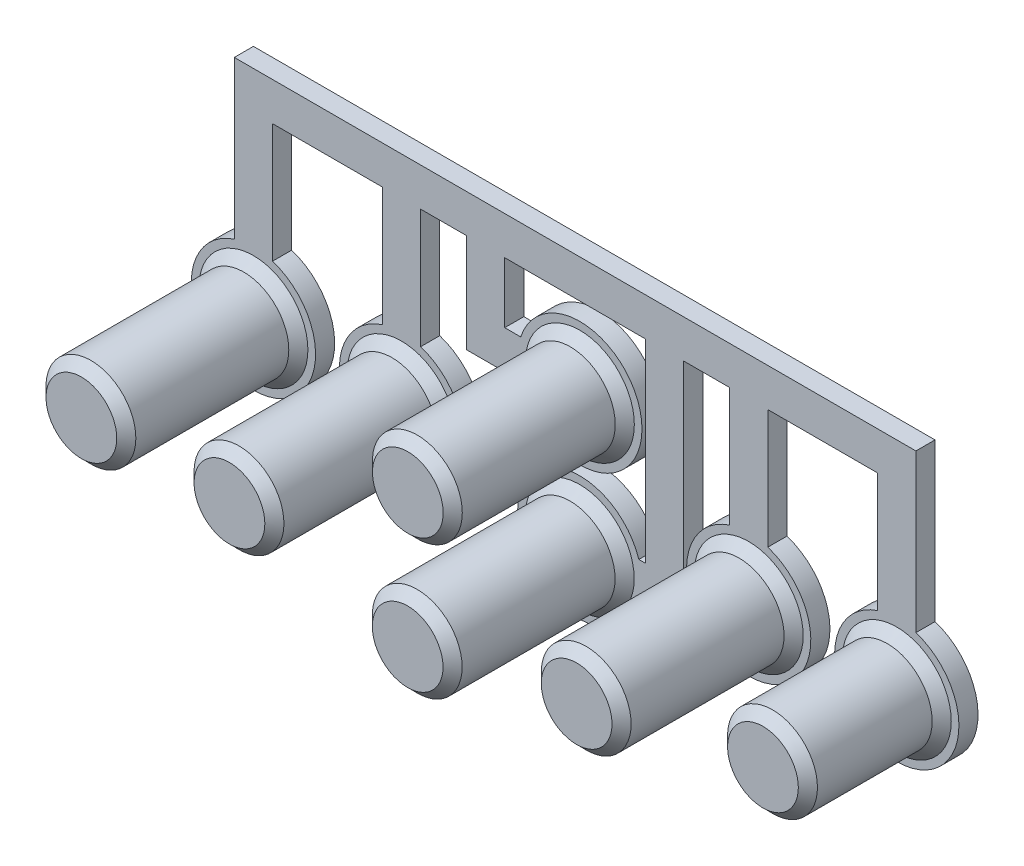
SolidWorks part; units mm, degrees
ref_plane "Front Plane" through (0, 0, 0) normal (0, 0, 1) x (1, 0, 0)
ref_plane "Top Plane" through (0, 0, 0) normal (0, 1, 0) x (1, 0, 0)
ref_plane "Right Plane" through (0, 0, 0) normal (1, 0, 0) x (0, 0, -1)
sketch "Skizze1" plane through (0, 0, 0) normal (0, 0, 1) x (1, 0, 0)
  line L0 (0.0076, 9.9935) -> (0.0076, 3.9935) construction
  line L1 (-2.9924, 9.9935) -> (3.0076, 9.9935) construction
  line L2 (3.0076, 3.9935) -> (-2.9924, 3.9935) construction
  line L3 (8.8392, 4.8386) -> (8.8392, -1.1614) construction
  line L4 (5.8392, 4.8386) -> (11.8392, 4.8386) construction
  line L5 (11.8392, -1.1614) -> (5.8392, -1.1614) construction
  line L6 (16.5862, 4.8386) -> (16.5862, -1.1614) construction
  line L7 (13.5862, 4.8386) -> (19.5862, 4.8386) construction
  line L8 (19.5862, -1.1614) -> (13.5862, -1.1614) construction
  line L9 (-9.3218, 4.8386) -> (-9.3218, -1.1614) construction
  line L10 (-12.3218, 4.8386) -> (-6.3218, 4.8386) construction
  line L11 (-6.3218, -1.1614) -> (-12.3218, -1.1614) construction
  line L12 (-17.0688, 4.8386) -> (-17.0688, -1.1614) construction
  line L13 (-20.0688, 4.8386) -> (-14.0688, 4.8386) construction
  line L14 (-14.0688, -1.1614) -> (-20.0688, -1.1614) construction
  circle A0 centre (0, 0) radius 2.35
  circle A1 centre (0.0076, 6.9935) radius 2.35
  circle A2 centre (8.8392, 1.8386) radius 2.35
  circle A3 centre (16.5862, 1.8386) radius 2.35
  circle A4 centre (-9.3218, 1.8386) radius 2.35
  circle A5 centre (-17.0688, 1.8386) radius 2.35
  dimension "D2" = 4.7
extrude "Aufsatz-Linear austragen1" add sketch "Skizze1" along normal blind 10 contours A5 | A4 | A0 | A1 | A2 region at (0, 0, 0) region at (0.0076, 6.9935, 0) region at (8.8392, 1.8386, 0) region at (-9.3218, 1.8386, 0) region at (-17.0688, 1.8386, 0)
extrude "Aufsatz-Linear austragen4" add sketch "Skizze1<3>" along normal blind 8 contours A3 region at (16.5862, 1.8386, 0)
sketch "Skizze1<3>" plane through (0, 0, 0) normal (0, 0, 1) x (1, 0, 0) same geometry as "Skizze1"
sketch "Skizze2" plane through (0, 0, 0) normal (0, 0, 1) x (1, 0, 0)
  circle A0 centre (-17.0688, 1.8386) radius 3.25
  circle A1 centre (-9.3218, 1.8386) radius 3.25
  circle A2 centre (0, 0) radius 3.25
  circle A3 centre (0.0076, 6.9935) radius 3.25
  circle A4 centre (8.8392, 1.8386) radius 3.25
  circle A5 centre (16.5862, 1.8386) radius 3.25
  dimension "D1" = 6.5
extrude "Aufsatz-Linear austragen2" add sketch "Skizze2" along normal blind 1
sketch "Skizze3" plane through (0, 0, 0) normal (0, 0, 1) x (1, 0, 0)
  line L0 (-17.0688, 1.8386) -> (-17.0688, 14.2266) construction
  line L1 (-18.0688, 13.1646) -> (-18.0688, 4.9309)
  line L2 (16.5862, 1.8386) -> (16.5862, 15.6024) construction
  line L3 (-18.0688, 13.1646) -> (17.5862, 13.1646)
  line L4 (17.5862, 13.1646) -> (17.5862, 4.9309)
  line L5 (-16.0688, 11.1646) -> (-16.0688, 4.9309)
  line L6 (-17.0688, 12.1646) -> (16.5862, 12.1646) construction
  line L7 (-16.0688, 11.1646) -> (-10.3218, 11.1646)
  line L8 (15.5862, 11.1646) -> (15.5862, 4.9309)
  line L9 (-16.0688, 11.1646) -> (-16.0688, 13.1646) construction
  line L10 (-9.3218, 1.8386) -> (-9.3218, 15.4604) construction
  line L11 (-8.3218, 11.1646) -> (-8.3218, 4.9309)
  line L12 (-10.3218, 11.1646) -> (-10.3218, 4.9309)
  line L13 (-8.3218, 11.1646) -> (-5.9218, 11.1646)
  line L14 (-4.9218, 11.1646) -> (-4.9218, 0.7573) construction
  line L15 (0.0076, 6.9935) -> (-4.9218, 6.9935) construction
  line L16 (-3.9218, 7.9935) -> (-3.0848, 7.9935)
  line L17 (-5.9218, 5.9935) -> (-3.0848, 5.9935)
  line L18 (-3.9218, 7.9935) -> (-3.9218, 11.1646)
  line L19 (-5.9218, 5.9935) -> (-5.9218, 11.1646)
  line L20 (4.4392, 11.1646) -> (4.4392, -2.7981) construction
  line L21 (0, 0) -> (4.4392, 0) construction
  line L22 (3.4392, -1) -> (3.0923, -1)
  line L23 (3.4392, 1) -> (3.0923, 1)
  line L24 (3.4392, -1) -> (5.4392, -1)
  line L25 (3.4392, 1) -> (3.4392, 11.1646)
  line L26 (5.4392, 1) -> (5.4392, 11.1646)
  line L27 (5.4392, 1) -> (5.4392, -1)
  line L28 (-3.9218, 11.1646) -> (3.4392, 11.1646)
  line L29 (5.4392, 11.1646) -> (7.8392, 11.1646)
  line L30 (8.8392, 1.8386) -> (8.8392, 11.1646) construction
  line L31 (9.8392, 11.1646) -> (9.8392, 4.9309)
  line L32 (7.8392, 11.1646) -> (7.8392, 4.9309)
  line L33 (9.8392, 11.1646) -> (15.5862, 11.1646)
  line L34 (-18.0688, 4.9309) -> (-16.0688, 4.9309)
  line L35 (-10.3218, 4.9309) -> (-8.3218, 4.9309)
  line L36 (-3.0848, 7.9935) -> (-3.0848, 5.9935)
  line L37 (3.0923, 1) -> (3.0923, -1)
  line L38 (7.8392, 4.9309) -> (9.8392, 4.9309)
  line L39 (17.5862, 4.9309) -> (15.5862, 4.9309)
  circle A0 centre (-17.0688, 1.8386) radius 3.25 construction
  circle A1 centre (16.5862, 1.8386) radius 3.25 construction
  circle A2 centre (-9.3218, 1.8386) radius 3.25 construction
  circle A3 centre (0.0076, 6.9935) radius 3.25 construction
  circle A4 centre (0, 0) radius 3.25 construction
  circle A5 centre (8.8392, 1.8386) radius 3.25 construction
  point P16 (-16.0688, 12.1646)
  dimension "D1" = 2
  dimension "D2" = 1
  dimension "D3" = 2
  dimension "D4" = 2
  dimension "D5" = 2
  dimension "D6" = 2
  dimension "D7" = 2
  dimension "D8" = 2
  dimension "D9" = 2
  dimension "D10" = 2.4
  dimension "D11" = 2.4
extrude "Aufsatz-Linear austragen3" add sketch "Skizze3" along normal up to surface (1 mm away) up to face at (-14.7188, 1.8386, 1)
chamfer "Fase1" distance 0.5 angle 45 5 edges at (11.1892, 1.8386, 10) (2.3576, 6.9935, 10) (2.35, 0, 10) (-6.9718, 1.8386, 10) (-14.7188, 1.8386, 10)
chamfer "Fase2" distance 0.5 angle 45 6 edges at (11.1892, 1.8386, 1) (2.35, 0, 1) (2.3576, 6.9935, 1) (-6.9718, 1.8386, 1) (-14.7188, 1.8386, 1) (18.9362, 1.8386, 1)
chamfer "Fase3" distance 0.5 angle 45 1 edges at (18.9362, 1.8386, 8)
